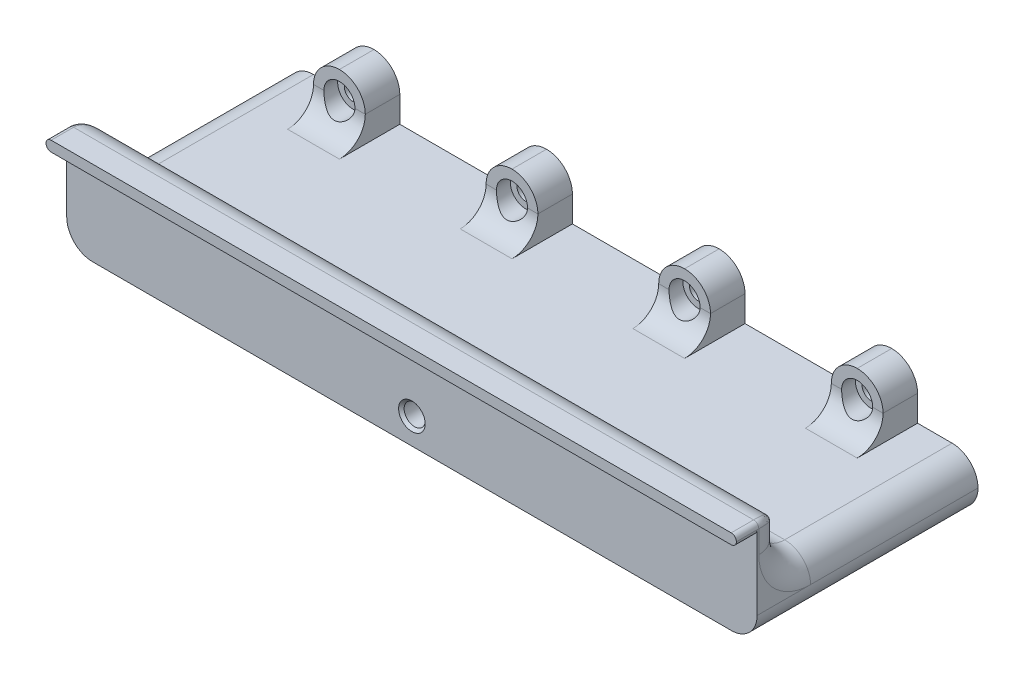
SolidWorks part; units mm, degrees
ref_plane "Front Plane" through (0, 0, 0) normal (0, 0, 1) x (1, 0, 0)
ref_plane "Top Plane" through (0, 0, 0) normal (0, 1, 0) x (1, 0, 0)
ref_plane "Right Plane" through (0, 0, 0) normal (1, 0, 0) x (0, 0, -1)
sketch "Sketch1" plane through (0, 0, 0) normal (0, 0, 1) x (1, 0, 0)
  line L5 (-100, -7.5) -> (100, -7.5)
  line L6 (-100, -7.5) -> (-100, 7.5)
  line L7 (-100, 7.5) -> (100, 7.5)
  line L8 (100, -7.5) -> (100, 7.5)
  line L9 (-100, -7.5) -> (100, 7.5) construction
  line L10 (-100, 7.5) -> (100, -7.5) construction
  line L11 (-82.5, 22.5) -> (-67.5, 22.5)
  line L12 (-82.5, 22.5) -> (-82.5, 7.5)
  line L13 (-82.5, 7.5) -> (-67.5, 7.5)
  line L14 (-67.5, 22.5) -> (-67.5, 7.5)
  line L15 (-82.5, 22.5) -> (-67.5, 7.5) construction
  line L16 (-82.5, 7.5) -> (-67.5, 22.5) construction
  line L17 (-32.5, 7.5) -> (-17.5, 7.5)
  line L18 (-32.5, 7.5) -> (-32.5, 22.5)
  line L19 (-32.5, 22.5) -> (-17.5, 22.5)
  line L20 (-17.5, 7.5) -> (-17.5, 22.5)
  line L21 (-32.5, 7.5) -> (-17.5, 22.5) construction
  line L22 (-32.5, 22.5) -> (-17.5, 7.5) construction
  line L23 (17.5, 7.5) -> (32.5, 7.5)
  line L24 (17.5, 7.5) -> (17.5, 22.5)
  line L25 (17.5, 22.5) -> (32.5, 22.5)
  line L26 (32.5, 7.5) -> (32.5, 22.5)
  line L27 (17.5, 7.5) -> (32.5, 22.5) construction
  line L28 (17.5, 22.5) -> (32.5, 7.5) construction
  line L29 (67.5, 7.5) -> (82.5, 7.5)
  line L30 (67.5, 7.5) -> (67.5, 22.5)
  line L31 (67.5, 22.5) -> (82.5, 22.5)
  line L32 (82.5, 7.5) -> (82.5, 22.5)
  line L33 (67.5, 7.5) -> (82.5, 22.5) construction
  line L34 (67.5, 22.5) -> (82.5, 7.5) construction
  circle A0 centre (75, 15) radius 2.6
  circle A1 centre (25, 15) radius 2.6
  circle A2 centre (-25, 15) radius 2.6
  circle A3 centre (-75, 15) radius 2.6
  point P0 (0, 0)
  point P1 (0, 0)
  dimension "D3" = 5.2
  dimension "D5" = 200
  dimension "D1" = 15
  dimension "D2" = 15
  dimension "D4" = 75
  dimension "D7" = 25
  dimension "D8" = 15
  dimension "D9" = 15
  dimension "D11" = 15
  dimension "D6" = 4
extrude "Boss-Extrude1" add sketch "Sketch1" along normal blind 6 contours L7 L20 L19 L18 A2 | L7 L26 L25 L24 A1 | L14 L11 L12 L7 A3 | L7 L32 L31 L30 A0 region at (-82.2879, 15, 0) region at (75, 7.7121, 0) region at (-32.2879, 15, 0) region at (25, 7.7121, 0)
extrude "Boss-Extrude2" add sketch "Sketch1<4>" along normal blind 64 contours L32 L29 L30 L7 L6 L5 L8 region at (0, 0, 0)
sketch "Sketch1<4>" plane through (0, 0, 0) normal (0, 0, 1) x (1, 0, 0) same geometry as "Sketch1"
sketch "Sketch2" plane through (0, 0, 64) normal (0, 0, 1) x (1, 0, 0)
  circle A0 centre (0, 0) radius 3.05
  dimension "D1" = 6.1
extrude "Cut-Extrude1" cut sketch "Sketch2" against normal blind 8
sketch "Sketch3" plane through (0, 0, 6) normal (0, 0, 1) x (1, 0, 0)
  line L0 (67.5, 7.5) -> (82.5, 7.5) construction
  line L1 (82.5, 7.5) -> (82.5, 22.5) construction
  line L2 (82.5, 22.5) -> (67.5, 22.5) construction
  line L3 (67.5, 22.5) -> (67.5, 7.5) construction
  line L4 (17.5, 7.5) -> (32.5, 7.5) construction
  line L5 (32.5, 7.5) -> (32.5, 22.5) construction
  line L6 (32.5, 22.5) -> (17.5, 22.5) construction
  line L7 (17.5, 22.5) -> (17.5, 7.5) construction
  line L8 (-32.5, 7.5) -> (-17.5, 7.5) construction
  line L9 (-17.5, 7.5) -> (-17.5, 22.5) construction
  line L10 (-17.5, 22.5) -> (-32.5, 22.5) construction
  line L11 (-32.5, 22.5) -> (-32.5, 7.5) construction
  line L12 (-67.5, 7.5) -> (-67.5, 22.5) construction
  line L13 (-67.5, 22.5) -> (-82.5, 22.5) construction
  line L14 (-82.5, 22.5) -> (-82.5, 7.5) construction
  line L15 (-82.5, 7.5) -> (-67.5, 7.5) construction
  line L16 (67.5, 7.5) -> (82.5, 7.5)
  line L17 (82.5, 7.5) -> (82.5, 22.5)
  line L18 (82.5, 22.5) -> (67.5, 22.5)
  line L19 (67.5, 22.5) -> (67.5, 7.5)
  line L20 (17.5, 7.5) -> (32.5, 7.5)
  line L21 (32.5, 7.5) -> (32.5, 22.5)
  line L22 (32.5, 22.5) -> (17.5, 22.5)
  line L23 (17.5, 22.5) -> (17.5, 7.5)
  line L24 (-32.5, 7.5) -> (-17.5, 7.5)
  line L25 (-17.5, 7.5) -> (-17.5, 22.5)
  line L26 (-17.5, 22.5) -> (-32.5, 22.5)
  line L27 (-32.5, 22.5) -> (-32.5, 7.5)
  line L28 (-67.5, 7.5) -> (-67.5, 22.5)
  line L29 (-67.5, 22.5) -> (-82.5, 22.5)
  line L30 (-82.5, 22.5) -> (-82.5, 7.5)
  line L31 (-82.5, 7.5) -> (-67.5, 7.5)
  circle A0 centre (-75, 15) radius 4.5
  circle A1 centre (-25, 15) radius 4.5
  circle A2 centre (25, 15) radius 4.5
  circle A3 centre (75, 15) radius 4.5
  dimension "D1" = 9
extrude "Boss-Extrude3" add sketch "Sketch3" along normal blind 4
chamfer "Chamfer1" distance 0.8 angle 45 1 edges at (3.05, 0, 64)
sketch "Sketch4" plane through (0, 7.5, 0) normal (0, 1, 0) x (1, 0, 0)
  line L1 (-100, -64) -> (100, -64)
  line L2 (-100, -64) -> (-100, -56)
  line L3 (-100, -56) -> (100, -56)
  line L4 (100, -64) -> (100, -56)
  line L5 (100, -64) -> (100, 0) construction
  dimension "D1" = 8
  dimension "D2" = 200
extrude "Boss-Extrude4" add sketch "Sketch4" along normal blind 15.5
sketch "Sketch5" plane through (0, 0, 64) normal (0, 0, 1) x (1, 0, 0)
  line L1 (-100, 23) -> (100, 23)
  line L2 (-100, 23) -> (-100, 20)
  line L3 (-100, 20) -> (100, 20)
  line L4 (100, 23) -> (100, 20)
  line L5 (100, -7.5) -> (100, 23) construction
  dimension "D1" = 3
  dimension "D2" = 200
extrude "Boss-Extrude5" add sketch "Sketch5" along normal blind 6
fillet "Fillet3" radius 7.5 20 edges at (100, -7.5, 32) (-100, -7.5, 32) (-100, 7.5, 28) (-75, 7.5, 10) (-25, 7.5, 10) (25, 7.5, 10) (75, 7.5, 10) (67.5, 22.5, 5) (-82.5, 22.5, 5) (-67.5, 22.5, 5) (17.5, 22.5, 5) (-32.5, 22.5, 5) (-17.5, 22.5, 5) (32.5, 22.5, 5) (100, 7.5, 28) (82.5, 22.5, 5) (100, 15.25, 56) (-100, 15.25, 56) (0, 7.5, 56) (0, 23, 56)
fillet "Fillet4" radius 1.5 6 edges at (-97.8033, 20.8033, 58.1967) (97.8033, 20.8033, 58.1967) (-100, 20, 67) (-100, 23, 66.75) (100, 23, 66.75) (100, 20, 67)
